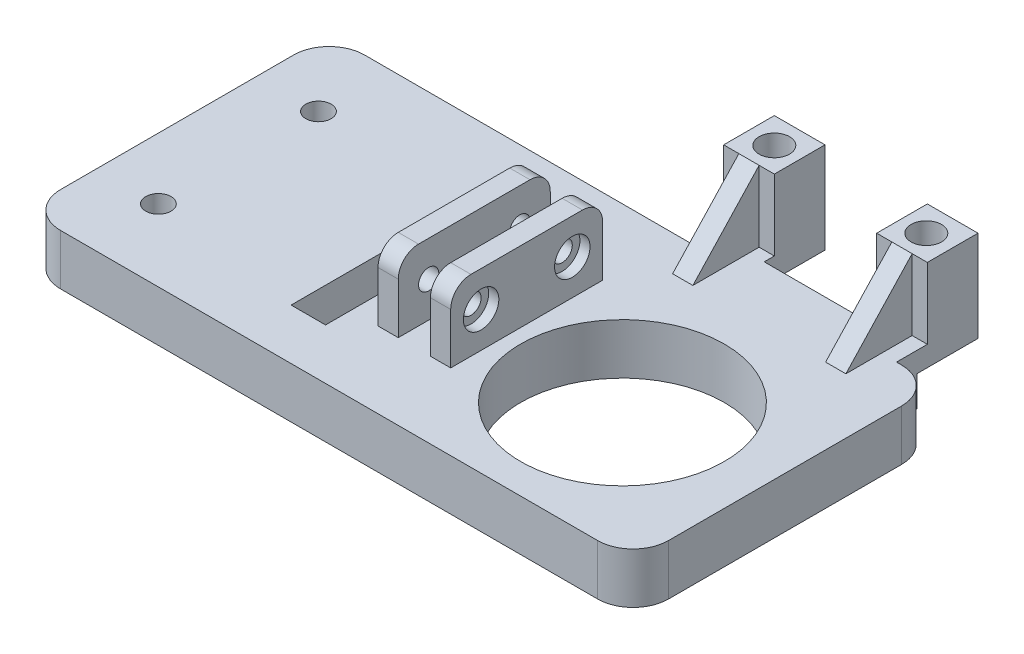
SolidWorks part; units mm, degrees
ref_plane "Front Plane" through (0, 0, 0) normal (0, 0, 1) x (1, 0, 0)
ref_plane "Top Plane" through (0, 0, 0) normal (0, 1, 0) x (1, 0, 0)
ref_plane "Right Plane" through (0, 0, 0) normal (1, 0, 0) x (0, 0, -1)
sketch "Sketch1" plane through (0, 0, 0) normal (0, 1, 0) x (1, 0, 0)
  line L1 (-30, 15) -> (30, 15)
  line L2 (-30, 15) -> (-30, -15)
  line L3 (-30, -15) -> (30, -15)
  line L4 (30, 15) -> (30, -15)
  line L5 (-30, 15) -> (30, -15) construction
  line L6 (-30, -15) -> (30, 15) construction
  point P0 (0, 0)
  dimension "D1" = 60
  dimension "D2" = 30
extrude "Boss-Extrude1" add sketch "Sketch1" along normal blind 5
sketch "Sketch2" plane through (0, 5, 0) normal (0, 1, 0) x (1, 0, 0)
  line L0 (-30, 15) -> (-30, -15) construction
  line L1 (-8.75, -10) -> (-5.35, -10)
  line L2 (-8.75, -10) -> (-8.75, 10)
  line L3 (-8.75, 10) -> (-5.35, 10)
  line L4 (-5.35, -10) -> (-5.35, 10)
  line L5 (-23.95, 7.9) -> (-23.95, -7.9) construction
  circle A0 centre (-23.95, -7.9) radius 1.25
  circle A1 centre (-23.95, 7.9) radius 1.25
  point P8 (-23.95, 0)
  point P9 (-8.75, 0)
  point P10 (-30, 0)
  dimension "D2" = 2.5
  dimension "D1" = 15.8
  dimension "D3" = 3.4
  dimension "D4" = 21.25
  dimension "D5" = 15.2
  dimension "D6" = 20
extrude "Cut-Extrude1" cut sketch "Sketch2" against normal through all
sketch "Sketch3" plane through (0, 0, 0) normal (0, -1, 0) x (1, 0, 0)
  line L0 (30, 15) -> (30, -15) construction
  line L1 (-30, 15) -> (30, 15) construction
  circle A0 centre (15.95, 2) radius 10.05
  dimension "D1" = 20.1
  dimension "D2" = 14.05
  dimension "D3" = 13
extrude "Cut-Extrude2" cut sketch "Sketch3" against normal through all
sketch "Sketch4" plane through (0, 0, -15) normal (0, 0, -1) x (-1, 0, 0)
  line L0 (-30, 5) -> (30, 5) construction
  line L1 (-26, 5) -> (-5.9, 5)
  line L2 (-26, 5) -> (-26, 0)
  line L3 (-26, 0) -> (-5.9, 0)
  line L4 (-5.9, 5) -> (-5.9, 0)
  line L5 (-30, 0) -> (30, 0) construction
  line L6 (-30, 5) -> (-30, 0) construction
  dimension "D1" = 4
  dimension "D2" = 20.1
extrude "Boss-Extrude2" add sketch "Sketch4" along normal blind 8.04
sketch "Sketch5" plane through (0, 5, 0) normal (0, 1, 0) x (1, 0, 0)
  line L1 (26, 23.04) -> (21, 23.04)
  line L2 (26, 23.04) -> (26, 18.04)
  line L3 (26, 18.04) -> (21, 18.04)
  line L4 (21, 23.04) -> (21, 18.04)
  circle A0 centre (23.45, 20.49) radius 1.5
  dimension "D1" = 3
  dimension "D2" = 5
  dimension "D3" = 2.55
  dimension "D4" = 2.55
  dimension "D5" = 5
extrude "Boss-Extrude3" add sketch "Sketch5" along normal blind 7
ref_plane "Plane1" through (15.95, 0, 0) normal (-1, 0, 0) x (0, 0, 1)
sketch "Sketch6" plane through (0, 0, 0) normal (0, -1, 0) x (1, 0, 0)
  line L0 (26, -23.04) -> (5.9, -23.04) construction
  line L1 (21, -23.04) -> (10.9, -23.04)
  line L2 (21, -23.04) -> (21, -17.04)
  line L3 (21, -17.04) -> (10.9, -17.04)
  line L4 (10.9, -23.04) -> (10.9, -17.04)
  line L5 (26, -23.04) -> (26, -15) construction
  line L6 (5.9, -23.04) -> (5.9, -15) construction
  circle A0 centre (23.45, -20.49) radius 1.5
  circle A1 centre (8.45, -20.49) radius 1.5
  point P11 (15.95, -23.04)
  point P12 (15.95, -17.04)
  dimension "D1" = 3
  dimension "D2" = 6
  dimension "D3" = 10.1
  dimension "D4" = 2.55
  dimension "D5" = 2.55
  dimension "D6" = 2.55
extrude "Cut-Extrude3" cut sketch "Sketch6" against normal blind 5
ref_plane "Plane2" through (23.5, 0, 0) normal (1, 0, 0) x (0, 0, -1)
sketch "Sketch8" plane through (23.5, 0, 0) normal (1, 0, 0) x (0, 0, -1)
  line L0 (18.04, 12) -> (11.5, 5)
  line L1 (18.04, 12) -> (18.04, 5) construction
  line L2 (-15, 5) -> (15, 5) construction
  line L4 (18.04, 5) -> (15, 5) construction
  dimension "D1" = 3.5
  dimension "D2" = 7
rib "Rib7" sketch "Sketch8" sketch "Sketch8" thickness 2 extrusion direction parallel to sketch draft on no parameters "D1"=2
sketch "Sketch9" plane through (0, 0, 0) normal (0, -1, 0) x (1, 0, 0)
  line L0 (26, -23.04) -> (26, -15) construction
  line L1 (26, -17.04) -> (21, -17.04)
  line L2 (26, -17.04) -> (26, -23.04)
  line L3 (26, -23.04) -> (21, -23.04)
  line L4 (21, -17.04) -> (21, -23.04)
extrude "Cut-Extrude4" cut sketch "Sketch9" against normal blind 3
mirror "Mirror1" about plane through (15.95, 0, 0) normal (-1, 0, 0) of "Cut-Extrude4", "Boss-Extrude3", "Rib7"
sketch "Sketch10" plane through (0, 5, 0) normal (0, 1, 0) x (1, 0, 0)
  line L0 (0.9125, -11.5514) -> (0.9125, 11.1943) construction
  line L1 (4.5, -7.5) -> (2.5, -7.5)
  line L2 (4.5, -7.5) -> (4.5, 7.5)
  line L3 (4.5, 7.5) -> (2.5, 7.5)
  line L4 (2.5, -7.5) -> (2.5, 7.5)
  line L5 (-0.675, -7.5) -> (-2.675, -7.5)
  line L6 (-0.675, -7.5) -> (-0.675, 7.5)
  line L7 (-0.675, 7.5) -> (-2.675, 7.5)
  line L8 (-2.675, -7.5) -> (-2.675, 7.5)
  line L10 (30, -15) -> (30, 15) construction
  point P12 (4.5, 0)
  point P13 (30, 0)
  dimension "D1" = 3.175
  dimension "D2" = 2
  dimension "D3" = 15
  dimension "D4" = 25.5
extrude "Boss-Extrude4" add sketch "Sketch10" along normal blind 7
sketch "Sketch11" plane through (4.5, 0, 0) normal (1, 0, 0) x (0, 0, -1)
  line L0 (-7.5, 12) -> (-7.5, 5) construction
  line L1 (7.5, 12) -> (7.5, 5) construction
  circle A0 centre (4.5, 8.5) radius 1.75
  circle A1 centre (-4.5, 8.5) radius 1.75
  point P7 (-7.5, 8.5)
  dimension "D1" = 3.5
  dimension "D2" = 3
  dimension "D3" = 3
extrude "Cut-Extrude5" cut sketch "Sketch11" against normal blind 1
sketch "Sketch12" plane through (3.5, 0, 0) normal (1, 0, 0) x (0, 0, -1)
  circle A0 centre (-4.5, 8.5) radius 1
  circle A1 centre (4.5, 8.5) radius 1
  dimension "D1" = 2
extrude "Cut-Extrude6" cut sketch "Sketch12" against normal blind 11
fillet "Fillet1" radius 3.5 4 edges at (-30, 2.5, 15) (-30, 2.5, -15) (30, 2.5, 15) (30, 2.5, -15)
fillet "Fillet2" radius 2 4 edges at (-1.675, 12, 7.5) (3.5, 12, 7.5) (-1.675, 12, -7.5) (3.5, 12, -7.5)
